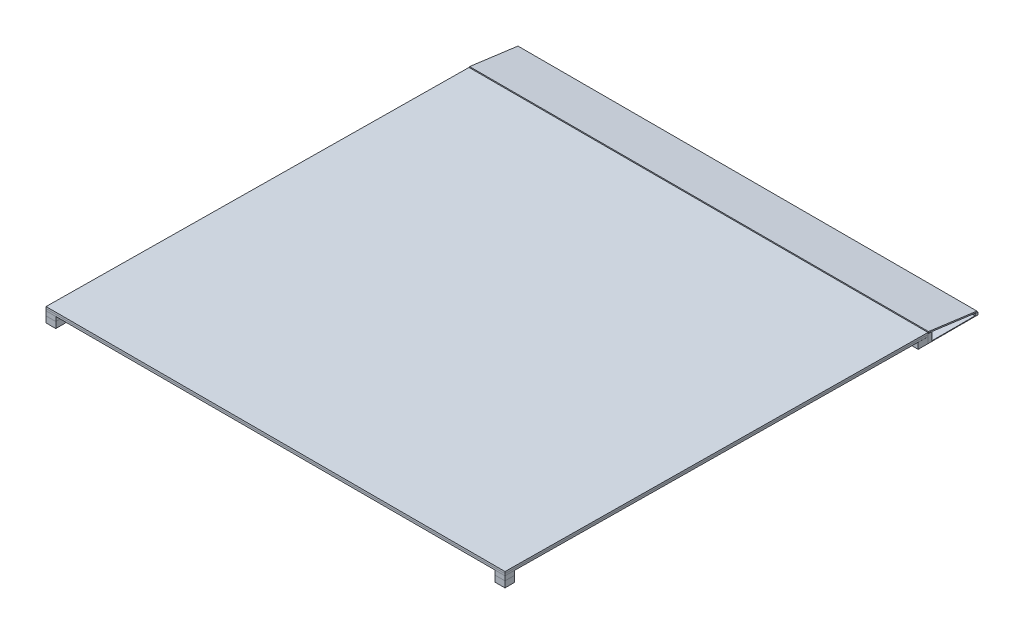
SolidWorks part; units mm, degrees
material "Pine"
ref_plane "Front" through (0, 0, 0) normal (0, 0, 1) x (1, 0, 0)
ref_plane "Top" through (0, 0, 0) normal (0, 1, 0) x (1, 0, 0)
ref_plane "Right" through (0, 0, 0) normal (1, 0, 0) x (0, 0, -1)
sketch "Sketch1" plane through (0, 0, 0) normal (0, 1, 0) x (1, 0, 0)
  line L1 (-2438.4, 2222.5) -> (2438.4, 2222.5) construction
  line L2 (-2438.4, 2222.5) -> (-2438.4, -2222.5) construction
  line L3 (-2438.4, -2222.5) -> (2438.4, -2222.5) construction
  line L4 (2438.4, 2222.5) -> (2438.4, -2222.5) construction
  line L5 (-2438.4, 2222.5) -> (2438.4, -2222.5) construction
  line L6 (-2438.4, -2222.5) -> (2438.4, 2222.5) construction
  point P0 (0, 0)
  dimension "D1" = 4876.8
  dimension "D2" = 4445
ref_plane "Plane1" through (0, 0, -2222.5) normal (0, 0, 1) x (1, 0, 0)
ref_plane "Plane2" through (0, 0, 2222.5) normal (0, 0, 1) x (1, 0, 0)
ref_plane "Plane3" through (-2438.4, 0, 0) normal (-1, 0, 0) x (0, 0, 1)
ref_plane "Plane4" through (2438.4, 0, 0) normal (-1, 0, 0) x (0, 0, 1)
sketch "Sketch2" plane through (2438.4, 0, 0) normal (-1, 0, 0) x (0, 0, 1)
  line L0 (-2178.05, 0) -> (-1015.9443, 12.17)
  line L1 (-2222.5, 0) -> (2222.5, 0) construction
  line L2 (-1015.9443, 12.17) -> (1015.9443, 33.4487)
  line L3 (1015.9443, 33.4487) -> (2222.5, 46.0841)
  line L4 (2222.5, -2682.24) -> (2222.5, 2682.24) construction
  line L5 (2222.5, 0) -> (-2222.5, 0) construction
  line L6 (0, 0) -> (0, 22.8093) construction
  line L7 (-2222.5, -2682.24) -> (-2222.5, 2682.24) construction
  dimension "D1" = 0.6
  dimension "D2" = 2032
  dimension "D3" = 4400.7913
  dimension "D4" = 44.45
  dimension "D5" = 46.0841
extrude "Extrude-Thin1" add sketch "Sketch2" along normal blind 4775.2 thin thin type one direction reverse wall 19.05
sketch "Sketch3" plane through (0, 0, 0) normal (0, 1, 0) x (1, 0, 0)
  line L13 (-2336.8, -2222.5) -> (-2235.2, -2222.5)
  line L14 (-2336.8, -2222.5) -> (-2336.8, -2120.9)
  line L15 (-2336.8, -2120.9) -> (-2235.2, -2120.9)
  line L16 (-2235.2, -2222.5) -> (-2235.2, -2120.9)
  line L21 (2438.4, -2222.5) -> (2336.8, -2222.5)
  line L22 (2438.4, -2222.5) -> (2438.4, -2120.9)
  line L23 (2438.4, -2120.9) -> (2336.8, -2120.9)
  line L24 (2336.8, -2222.5) -> (2336.8, -2120.9)
  point P0 (-1869.3553, -1879.5929)
  dimension "D1" = 101.6
extrude "Boss-Extrude1" add sketch "Sketch3" along normal up to surface (46.0841 mm away) separate body up to face at (50.8, 23.0421, 22.225)
sketch "Sketch5" plane through (-2438.4, 0, 0) normal (-1, 0, 0) x (0, 0, 1)
  line L0 (-2222.5, 76.2) -> (-2222.5, 0)
  line L1 (-2222.5, -2682.24) -> (-2222.5, 2682.24) construction
  line L2 (2222.5, 0) -> (-2222.5, 0) construction
  line L3 (-2222.5, 0) -> (-2178.2495, 0)
  line L4 (-2178.2495, 0) -> (-2178.2495, 19.05)
  line L5 (-2178.2495, 19.05) -> (-2184.5995, 19.05)
  line L6 (-2184.5995, 19.05) -> (-2184.5995, 6.35)
  line L7 (-2184.5995, 6.35) -> (-2216.15, 6.35)
  line L8 (-2216.15, 6.35) -> (-2216.15, 76.2)
  line L9 (-2216.15, 76.2) -> (-2222.5, 76.2)
  line L10 (-2184.5995, 6.35) -> (-2184.5995, 0) construction
  dimension "D1" = 6.35
  dimension "D2" = 76.2
  dimension "D3" = 12.7
extrude "Boss-Extrude3" [suppressed] add sketch "Sketch5" against normal up to surface (4876.8 mm away) separate body up to face at (2438.4, 32.5665, 22.1253)
sketch "Sketch6" plane through (0, 0, 0) normal (0, -1, 0) x (1, 0, 0)
  line L1 (-2336.8, -2178.05) -> (-2235.2, -2178.05)
  line L2 (-2336.8, -2178.05) -> (-2336.8, -2076.45)
  line L3 (-2336.8, -2076.45) -> (-2235.2, -2076.45)
  line L4 (2438.4, 2120.9) -> (2438.4, 2222.5)
  line L5 (2438.4, 2222.5) -> (2336.8, 2222.5)
  line L6 (2336.8, 2222.5) -> (2336.8, 2120.9)
  line L7 (2336.8, 2120.9) -> (2438.4, 2120.9)
  line L8 (2438.4, 2120.9) -> (2438.4, 2222.5)
  line L9 (2438.4, 2222.5) -> (2336.8, 2222.5)
  line L10 (2336.8, 2222.5) -> (2336.8, 2120.9)
  line L11 (2336.8, 2120.9) -> (2438.4, 2120.9)
  line L12 (-2336.8, 2222.5) -> (-2336.8, 2120.9)
  line L13 (-2336.8, 2120.9) -> (-2235.2, 2120.9)
  line L14 (-2235.2, 2120.9) -> (-2235.2, 2222.5)
  line L15 (-2235.2, 2222.5) -> (-2336.8, 2222.5)
  line L16 (-2336.8, 2222.5) -> (-2336.8, 2120.9)
  line L17 (-2336.8, 2120.9) -> (-2235.2, 2120.9)
  line L18 (-2235.2, 2120.9) -> (-2235.2, 2222.5)
  line L19 (-2235.2, 2222.5) -> (-2336.8, 2222.5)
  line L20 (-2235.2, -2178.05) -> (-2235.2, -2076.45)
  line L21 (2438.4, -2178.05) -> (2336.8, -2178.05)
  line L22 (2438.4, -2178.05) -> (2438.4, -2076.45)
  line L23 (2438.4, -2076.45) -> (2336.8, -2076.45)
  line L24 (2336.8, -2178.05) -> (2336.8, -2076.45)
  dimension "D1" = 0
  dimension "D2" = 0
extrude "Boss-Extrude4" add sketch "Sketch6" along normal blind 63.5
sketch "Sketch8" plane through (0, 41.8558, -0.4383) normal (0, 0.9999, -0.0105) x (1, 0, 0)
  line L4 (2438.4, -2222.8607) -> (2438.4, 2177.9306)
  line L5 (2438.4, 2177.9306) -> (-2336.8, 2177.9306)
  line L6 (-2336.8, 2177.9306) -> (-2336.8, -2222.8607)
  line L7 (-2336.8, -2222.8607) -> (2438.4, -2222.8607)
  line L8 (2438.4, -2222.8607) -> (2438.4, 2177.9306)
  line L9 (2438.4, 2177.9306) -> (-2336.8, 2177.9306)
  line L10 (-2336.8, 2177.9306) -> (-2336.8, -2222.8607)
  line L11 (-2336.8, -2222.8607) -> (2438.4, -2222.8607)
  dimension "D1" = 0
extrude "Boss-Extrude5" add sketch "Sketch8" along normal blind 19.05 separate body
sketch "Sketch7" plane through (0, 0, -2178.05) normal (0, 0, -1) x (-1, 0, 0)
  line L5 (-2438.4, -63.5) -> (2336.8, -63.5)
  line L6 (-2438.4, -63.5) -> (-2438.4, 25.4)
  line L7 (-2438.4, 25.4) -> (2336.8, 25.4)
  line L8 (2336.8, -63.5) -> (2336.8, 25.4)
  point P6 (0, 0)
  dimension "D1" = 88.9
extrude "Boss-Extrude6" add sketch "Sketch7" along normal blind 38.1 separate body
sketch "Sketch9" plane through (0, 0, -2216.15) normal (0, 0, -1) x (-1, 0, 0)
  line L0 (2336.8, -63.5) -> (2336.8, 25.4) construction
  line L1 (-2438.4, -63.5) -> (2336.8, -63.5)
  line L2 (-2438.4, -63.5) -> (-2438.4, -38.1)
  line L3 (-2438.4, -38.1) -> (2336.8, -38.1)
  line L4 (2336.8, -63.5) -> (2336.8, -38.1)
  dimension "D1" = 25.4
extrude "Boss-Extrude8" add sketch "Sketch9" along normal blind 25.4 from offset 457.2 separate body
sketch "Sketch10" plane through (2438.4, 0, 0) normal (1, 0, 0) x (0, 0, -1)
  line L0 (2216.15, 25.4) -> (2216.15, -63.5)
  line L1 (2216.15, -63.5) -> (2673.35, -63.5)
  line L2 (2673.35, -63.5) -> (2673.35, -38.1)
  line L3 (2673.35, -38.1) -> (2667, -38.1)
  line L4 (2667, -38.1) -> (2667, -57.15)
  line L5 (2667, -57.15) -> (2222.5, -57.15)
  line L6 (2222.5, -57.15) -> (2222.5, 25.4)
  line L7 (2222.5, 25.4) -> (2216.15, 25.4)
  line L8 (2673.35, -38.1) -> (2673.35, -63.5) construction
  line L9 (2222.5, -57.15) -> (2222.5, -63.5) construction
  dimension "D1" = 6.35
extrude "Boss-Extrude9" add sketch "Sketch10" against normal up to vertex (4775.2 mm away) separate body up to point (-2336.8, 38.0979, -2178.449)
sketch "Sketch11" plane through (2438.4, 0, 0) normal (1, 0, 0) x (0, 0, -1)
  line L0 (2182.5062, 30.7325) -> (2686.05, -36.4067)
  line L1 (2686.05, -36.4067) -> (2687.7285, -23.8181)
  line L2 (2687.7285, -23.8181) -> (2184.1847, 43.3211)
  line L3 (2184.1847, 43.3211) -> (2182.5062, 30.7325)
  line L5 (2698.75, -38.1) -> (2698.75, -63.5) construction
  point P4 (2703.9403, -37.4968)
  point P5 (2697.7692, -37.9692)
  dimension "D1" = 12.7
  dimension "D2" = 508
  dimension "D3" = 12.7
extrude "Boss-Extrude10" add sketch "Sketch11" against normal up to vertex (4775.2 mm away) separate body up to point (-2336.8, -38.1, -2698.75)
